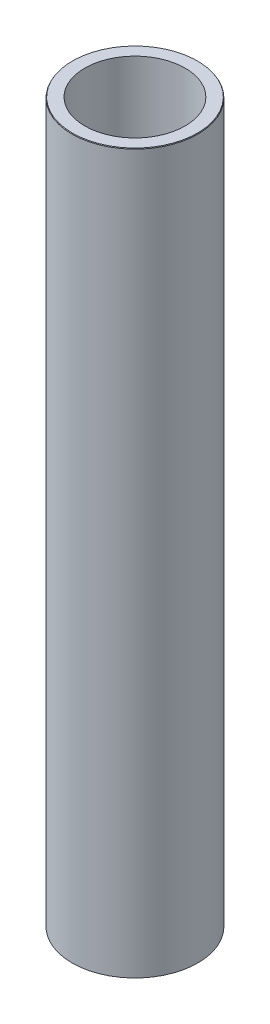
SolidWorks part; units mm, degrees
ref_plane "Front Plane" through (0, 0, 0) normal (0, 0, 1) x (1, 0, 0)
ref_plane "Top Plane" through (0, 0, 0) normal (0, 1, 0) x (1, 0, 0)
ref_plane "Right Plane" through (0, 0, 0) normal (1, 0, 0) x (0, 0, -1)
sketch "Sketch1" plane through (0, 0, 0) normal (0, 1, 0) x (1, 0, 0)
  circle A0 centre (0, 0) radius 52.5
  dimension "SHAFT_OD" = 105
extrude "Boss-Extrude1" add sketch "Sketch1" along normal blind 600
sketch "Sketch2" plane through (0, 0, 0) normal (0, 1, 0) x (1, 0, 0)
  circle A0 centre (0, 0) radius 41.8644
  dimension "BORE_D" = 83.7288
extrude "Cut-Extrude1" cut sketch "Sketch2" along normal through all
chamfer "Chamfer1" distance 0.5792 angle 30 2 edges at (0, 600, 52.5) (0, 0, 52.5) first distance on face at (0, 600, 52.5) first distance on face at (0, 0, 41.8644)
